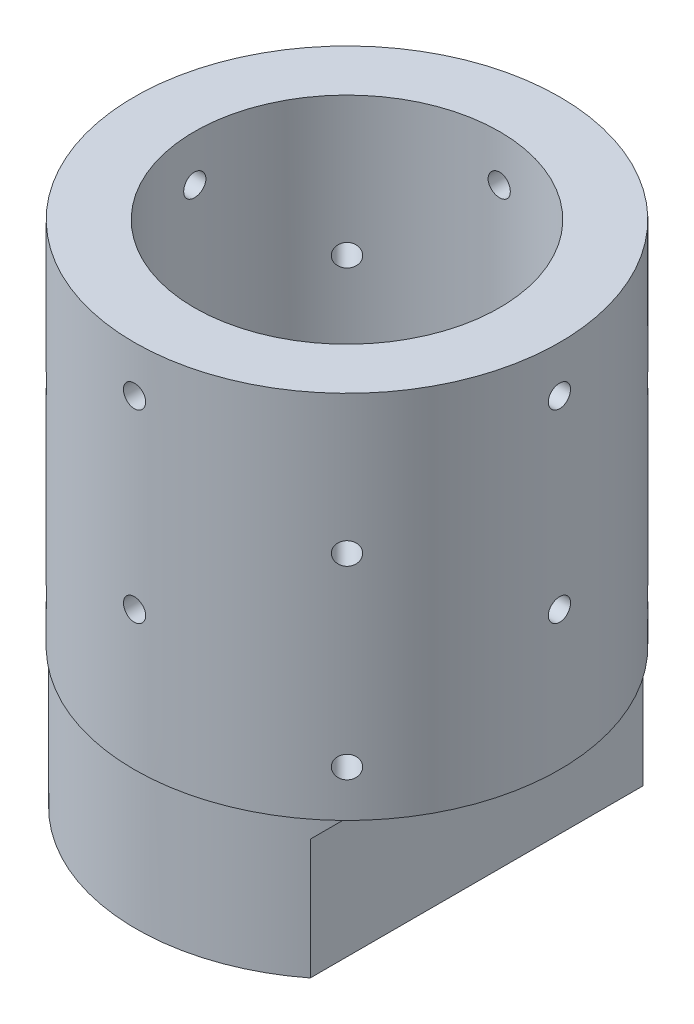
SolidWorks part; units mm, degrees
ref_plane "Спереди" through (0, 0, 0) normal (0, 0, 1) x (1, 0, 0)
ref_plane "Сверху" through (0, 0, 0) normal (0, 1, 0) x (1, 0, 0)
ref_plane "Справа" through (0, 0, 0) normal (1, 0, 0) x (0, 0, -1)
sketch "Эскиз1" plane through (0, 0, 0) normal (0, 1, 0) x (1, 0, 0)
  circle A0 centre (0, 0) radius 23
  dimension "D1" = 46
extrude "Бобышка-Вытянуть1" add sketch "Эскиз1" along normal blind 5
sketch "Эскиз2" plane through (0, 5, 0) normal (0, 1, 0) x (1, 0, 0)
  circle A0 centre (0, 0) radius 23
  circle A1 centre (0, 0) radius 16.5
  circle A2 centre (0, 0) radius 23 construction
  dimension "D1" = 33
  dimension "D2" = 0
extrude "Бобышка-Вытянуть2" add sketch "Эскиз2" along normal blind 35
sketch "Эскиз3" plane through (0, 0, 0) normal (1, 0, 0) x (0, 0, -1)
  line L0 (-23, 20) -> (28.0263, 20) construction
  line L1 (-23, 40) -> (-23, 0) construction
  line L2 (16.5, 40) -> (-16.5, 40) construction
  circle A1 centre (0, 35) radius 1.2
  dimension "D1" = 2.4
  dimension "D2" = 5
extrude "Вырез-Вытянуть1" cut sketch "Эскиз3" against normal through all
ref_plane "Плоскость1" through (0, 0, 0) normal (0.7071, 0, 0.7071) x (0, -1, 0)
sketch "Эскиз4" plane through (0, 0, 0) normal (0.7071, 0, 0.7071) x (0, -1, 0)
  line L0 (-20, 23) -> (-20, -30.0625) construction
  line L1 (0, 23) -> (-40, 23) construction
  line L3 (0, -23) -> (0, 23) construction
  circle A1 centre (-5, 0) radius 1.2
  dimension "D1" = 5
  dimension "D2" = 2.4
extrude "Вырез-Вытянуть2" cut sketch "Эскиз4" against normal through all from offset 16.3 offset against normal yes
pattern_circular "Круговой массив1" count 4 over 360 about axis through (0, 5, 0) along (0, -1, 0) of "Вырез-Вытянуть2"
pattern_circular "Круговой массив2" count 4 over 360 about axis through (0, 5, 0) along (0, -1, 0) of "Вырез-Вытянуть1"
pattern_linear "Линейный массив3" count 2 spacing 20 along (0, 1, 0) of "Круговой массив1"
pattern_linear "Линейный массив4" count 2 spacing 20 along (0, -1, 0) of "Круговой массив2"
sketch "Эскиз12" plane through (0, 0, 0) normal (0, -1, 0) x (1, 0, 0)
  line L1 (14.0272, 18) -> (14.0272, -18)
  line L20 (0, 15) -> (-2.7835, 17.7835)
  line L21 (-2.7835, -17.7835) -> (0, -15)
  line L22 (0, -15) -> (0, 15)
  line L23 (0, 15) -> (-2.7835, 17.7835)
  line L24 (-2.7835, -17.7835) -> (0, -15)
  line L25 (0, -15) -> (0, 15)
  arc A2 (14.0272, 18) -> (14.0272, -18) centre (0, 0) ccw
  arc A13 (-2.7835, 17.7835) -> (-2.7835, -17.7835) centre (0, 0) ccw
  arc A14 (-2.7835, 17.7835) -> (-2.7835, -17.7835) centre (0, 0) ccw
  dimension "D1" = 0
extrude "Бобышка-Вытянуть3" add sketch "Эскиз12" along normal blind 15 contours L1 A2 region at (13.4406, 0, 0)
sketch "Эскиз13" plane through (0, -15, 0) normal (0, -1, 0) x (1, 0, 0)
  line L14 (-2.6786, -18.1029) -> (0.3, -15.1243)
  line L15 (0.3, 15.1243) -> (-2.6786, 18.1029)
  line L16 (0.3, -15.1243) -> (0.3, 15.1243)
  line L17 (-2.6786, -18.1029) -> (0.3, -15.1243)
  line L18 (0.3, 15.1243) -> (-2.6786, 18.1029)
  line L19 (0.3, -15.1243) -> (0.3, 15.1243)
  arc A5 (-2.6786, 18.1029) -> (-2.6786, -18.1029) centre (0, 0) ccw
  arc A6 (-2.6786, 18.1029) -> (-2.6786, -18.1029) centre (0, 0) ccw
  dimension "D1" = 0.3
extrude "Вырез-Вытянуть10" cut sketch "Эскиз13" against normal up to surface (15 mm away) up to face at (0, 0, 23)
chamfer "Фаска4" distance 2 angle 45 1 edges at (14.0272, 0, 0)
chamfer "Фаска6" distance 2 angle 45 4 edges at (-1.1893, 0, -16.6136) (-18.3, 0, 0) (0.3, 0, 0) (-1.1893, 0, 16.6136)
chamfer "Фаска7" distance 2 angle 45 4 edges at (-1.1893, -15, -16.6136) (-18.3, -15, 0) (-1.1893, -15, 16.6136) (0.3, -15, 0)
